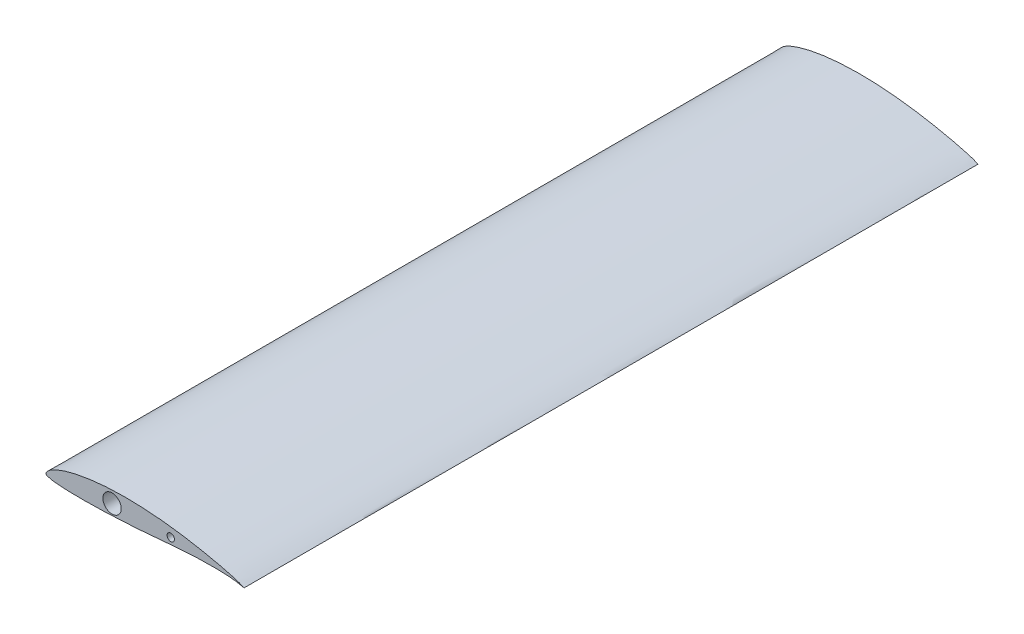
SolidWorks part; units mm, degrees
ref_plane "Front Plane" through (0, 0, 0) normal (0, 0, 1) x (1, 0, 0)
ref_plane "Top Plane" through (0, 0, 0) normal (0, 1, 0) x (1, 0, 0)
ref_plane "Right Plane" through (0, 0, 0) normal (1, 0, 0) x (0, 0, -1)
curve "Curve1"
  spline degree 3 poles (267.933, 0.5337, 0) (270.49, -0.1564, 0) (268.2375, 0.6665, 0) (266.5672, 1.4668, 0) (262.6756, 3.0154, 0) (257.9132, 4.5724, 0) (251.732, 6.3325, 0) (244.4112, 8.2376, 0) (235.9576, 10.2728, 0) (226.5142, 12.3893, 0) (216.1934, 14.5409, 0) (205.1313, 16.6775, 0) (193.4567, 18.7298, 0) (181.2977, 20.6324, 0) (168.7678, 22.3117, 0) (155.9753, 23.7079, 0) (143.0353, 24.8049, 0) (130.0617, 25.5802, 0) (117.1734, 26.0003, 0) (104.4837, 26.0576, 0) (92.1044, 25.7531, 0) (80.1395, 25.0742, 0) (68.69, 24.0381, 0) (57.8509, 22.6699, 0) (47.7143, 21.0125, 0) (38.3732, 19.0872, 0) (29.9084, 16.9558, 0) (22.399, 14.6444, 0) (15.9079, 12.2159, 0) (10.4843, 9.7202, 0) (6.177, 7.2209, 0) (2.9612, 4.7412, 0) (0.9766, 2.4261, 0) (0.0237, 0.7907, 0) (-0.0162, -0.4697, 0) (0.8003, -1.8361, 0) (3.4921, -2.6295, 0) (7.308, -3.6627, 0) (12.6566, -4.3991, 0) (19.3194, -5.0329, 0) (27.2905, -5.4698, 0) (36.4622, -5.7387, 0) (46.7414, -5.84, 0) (58.0105, -5.7702, 0) (70.1434, -5.5368, 0) (83.0071, -5.1408, 0) (96.4629, -4.5659, 0) (110.374, -3.827, 0) (124.6167, -2.893, 0) (139.0995, -1.7363, 0) (153.7348, -0.4008, 0) (168.4097, 0.8923, 0) (182.9339, 2.0414, 0) (197.0782, 2.9592, 0) (210.6044, 3.579, 0) (223.2667, 3.8744, 0) (234.8405, 3.8186, 0) (245.0477, 3.4533, 0) (253.7786, 2.7629, 0) (260.4407, 1.9422, 0) (265.7815, 0.9299, 0) (267.933, 0.5337, 0) (270.49, -0.1564, 0) (268.2375, 0.6665, 0) knots -0.016249 -0.007187 -0.001789 0 0.001694 0.006395 0.013462 0.022754 0.034367 0.048191 0.064031 0.081681 0.100894 0.121432 0.143025 0.165434 0.188439 0.211855 0.235496 0.259144 0.282615 0.305702 0.328232 0.35003 0.370944 0.390817 0.409506 0.426857 0.442733 0.457018 0.469615 0.48045 0.489472 0.49673 0.502329 0.506256 0.506442 0.509182 0.513914 0.521178 0.530944 0.543145 0.55767 0.574384 0.59311 0.613638 0.635744 0.659184 0.683714 0.709076 0.735036 0.76143 0.788184 0.815057 0.841645 0.867514 0.892232 0.915364 0.936485 0.9552 0.971104 0.983751 0.992813 0.998211 1 1.001694 1.006395 1.013462 periodic
sketch "Sketch1" plane through (0, 0, 0) normal (0, 0, 1) x (1, 0, 0)
  line L0 (270, 0) -> (0, 0) construction
  line L1 (0, -23.2448) -> (0, 51.8173) construction
  line L2 (90, 9.6033) -> (90, 0) construction
  line L3 (0, 26.0183) -> (162.1091, 26.0183) construction
  line L4 (0, -5.812) -> (132.6055, -5.812) construction
  circle A0 centre (90, 9.6033) radius 12.5
  circle A1 centre (170, 9.6033) radius 5
  spline S0 degree 3 poles (267.933, 0.5337) (270.49, -0.1564) (268.2375, 0.6665) (266.5672, 1.4668) (262.6756, 3.0154) (257.9132, 4.5724) (251.732, 6.3325) (244.4112, 8.2376) (235.9576, 10.2728) (226.5142, 12.3893) (216.1934, 14.5409) (205.1313, 16.6775) (193.4567, 18.7298) (181.2977, 20.6324) (168.7678, 22.3117) (155.9753, 23.7079) (143.0353, 24.8049) (130.0617, 25.5802) (117.1734, 26.0003) (104.4837, 26.0576) (92.1044, 25.7531) (80.1395, 25.0742) (68.69, 24.0381) (57.8509, 22.6699) (47.7143, 21.0125) (38.3732, 19.0872) (29.9084, 16.9558) (22.399, 14.6444) (15.9079, 12.2159) (10.4843, 9.7202) (6.177, 7.2209) (2.9612, 4.7412) (0.9766, 2.4261) (0.0237, 0.7907) (-0.0162, -0.4697) (0.8003, -1.8361) (3.4921, -2.6295) (7.308, -3.6627) (12.6566, -4.3991) (19.3194, -5.0329) (27.2905, -5.4698) (36.4622, -5.7387) (46.7414, -5.84) (58.0105, -5.7702) (70.1434, -5.5368) (83.0071, -5.1408) (96.4629, -4.5659) (110.374, -3.827) (124.6167, -2.893) (139.0995, -1.7363) (153.7348, -0.4008) (168.4097, 0.8923) (182.9339, 2.0414) (197.0782, 2.9592) (210.6044, 3.579) (223.2667, 3.8744) (234.8405, 3.8186) (245.0477, 3.4533) (253.7786, 2.7629) (260.4407, 1.9422) (265.7815, 0.9299) (267.933, 0.5337) (270.49, -0.1564) (268.2375, 0.6665) knots -0.016249 -0.007187 -0.001789 0 0.001694 0.006395 0.013462 0.022754 0.034367 0.048191 0.064031 0.081681 0.100894 0.121432 0.143025 0.165434 0.188439 0.211855 0.235496 0.259144 0.282615 0.305702 0.328232 0.35003 0.370944 0.390817 0.409506 0.426857 0.442733 0.457018 0.469615 0.48045 0.489472 0.49673 0.502329 0.506256 0.506442 0.509182 0.513914 0.521178 0.530944 0.543145 0.55767 0.574384 0.59311 0.613638 0.635744 0.659184 0.683714 0.709076 0.735036 0.76143 0.788184 0.815057 0.841645 0.867514 0.892232 0.915364 0.936485 0.9552 0.971104 0.983751 0.992813 0.998211 1 1.001694 1.006395 1.013462 only from (270, 0) to (270, 0) construction
  spline S1 degree 3 poles (267.933, 0.5337) (270.49, -0.1564) (268.2375, 0.6665) (266.5672, 1.4668) (262.6756, 3.0154) (257.9132, 4.5724) (251.732, 6.3325) (244.4112, 8.2376) (235.9576, 10.2728) (226.5142, 12.3893) (216.1934, 14.5409) (205.1313, 16.6775) (193.4567, 18.7298) (181.2977, 20.6324) (168.7678, 22.3117) (155.9753, 23.7079) (143.0353, 24.8049) (130.0617, 25.5802) (117.1734, 26.0003) (104.4837, 26.0576) (92.1044, 25.7531) (80.1395, 25.0742) (68.69, 24.0381) (57.8509, 22.6699) (47.7143, 21.0125) (38.3732, 19.0872) (29.9084, 16.9558) (22.399, 14.6444) (15.9079, 12.2159) (10.4843, 9.7202) (6.177, 7.2209) (2.9612, 4.7412) (0.9766, 2.4261) (0.0237, 0.7907) (-0.0162, -0.4697) (0.8003, -1.8361) (3.4921, -2.6295) (7.308, -3.6627) (12.6566, -4.3991) (19.3194, -5.0329) (27.2905, -5.4698) (36.4622, -5.7387) (46.7414, -5.84) (58.0105, -5.7702) (70.1434, -5.5368) (83.0071, -5.1408) (96.4629, -4.5659) (110.374, -3.827) (124.6167, -2.893) (139.0995, -1.7363) (153.7348, -0.4008) (168.4097, 0.8923) (182.9339, 2.0414) (197.0782, 2.9592) (210.6044, 3.579) (223.2667, 3.8744) (234.8405, 3.8186) (245.0477, 3.4533) (253.7786, 2.7629) (260.4407, 1.9422) (265.7815, 0.9299) (267.933, 0.5337) (270.49, -0.1564) (268.2375, 0.6665) knots -0.016249 -0.007187 -0.001789 0 0.001694 0.006395 0.013462 0.022754 0.034367 0.048191 0.064031 0.081681 0.100894 0.121432 0.143025 0.165434 0.188439 0.211855 0.235496 0.259144 0.282615 0.305702 0.328232 0.35003 0.370944 0.390817 0.409506 0.426857 0.442733 0.457018 0.469615 0.48045 0.489472 0.49673 0.502329 0.506256 0.506442 0.509182 0.513914 0.521178 0.530944 0.543145 0.55767 0.574384 0.59311 0.613638 0.635744 0.659184 0.683714 0.709076 0.735036 0.76143 0.788184 0.815057 0.841645 0.867514 0.892232 0.915364 0.936485 0.9552 0.971104 0.983751 0.992813 0.998211 1 1.001694 1.006395 1.013462 only from (270, 0) to (270, 0)
  point P12 (0, 0)
  dimension "D1" = 25
  dimension "D6" = 10
  dimension "D2" = 90
  dimension "D3" = 31.8303
  dimension "D4" = 16.415
  dimension "D5" = 80
extrude "Boss-Extrude1" add sketch "Sketch1" along normal blind 1000 contours S1
extrude "Cut-Extrude1" cut sketch "Sketch1<3>" along normal through all contours A0 | A1
sketch "Sketch1<3>" plane through (0, 0, 0) normal (0, 0, 1) x (1, 0, 0) same geometry as "Sketch1"
